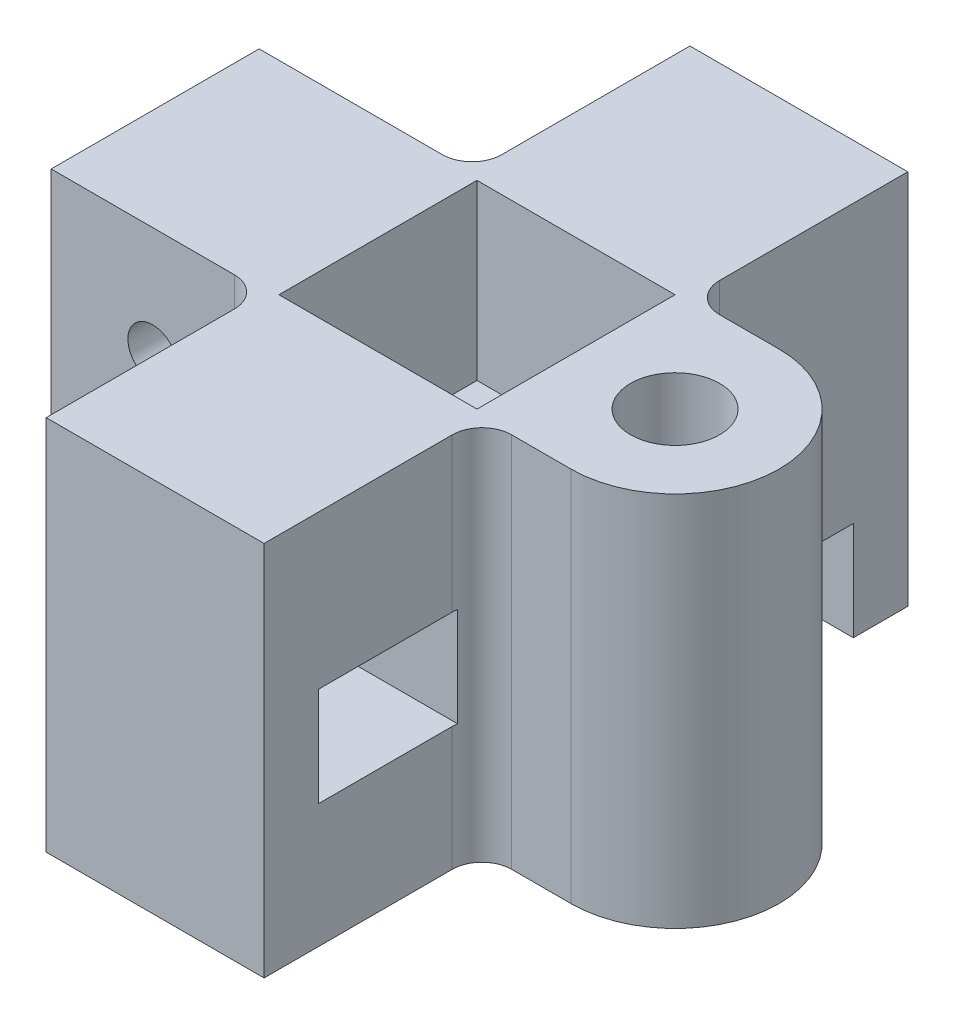
SolidWorks part; units mm, degrees
ref_plane "Front" through (0, 0, 0) normal (0, 0, 1) x (1, 0, 0)
ref_plane "Top" through (0, 0, 0) normal (0, 1, 0) x (1, 0, 0)
ref_plane "Right" through (0, 0, 0) normal (1, 0, 0) x (0, 0, -1)
sketch "Sketch1" plane through (0, 0, 0) normal (0, 1, 0) x (1, 0, 0)
  line L1 (-32.5, 32.5) -> (32.5, 32.5)
  line L2 (-32.5, 32.5) -> (-32.5, -32.5)
  line L3 (-32.5, -32.5) -> (32.5, -32.5)
  line L4 (32.5, 32.5) -> (32.5, -32.5)
  line L5 (-32.5, 32.5) -> (32.5, -32.5) construction
  line L6 (-32.5, -32.5) -> (32.5, 32.5) construction
  circle A0 centre (0, 0) radius 2.5
  circle A1 centre (20, 0) radius 2.5
  point P0 (0, 0)
  dimension "D3" = 5
  dimension "D1" = 65
  dimension "D2" = 65
  dimension "D4" = 20
extrude "Boss-Extrude1" add sketch "Sketch1" along normal blind 38
sketch "Sketch3" plane through (0, 38, 0) normal (0, 1, 0) x (1, 0, 0)
  line L0 (-32.5, 10.5) -> (-11, 10.5)
  line L1 (-32.5, 32.5) -> (-32.5, -32.5) construction
  line L2 (-11, 10.5) -> (-11, 32.5)
  line L3 (32.5, 32.5) -> (-32.5, 32.5) construction
  line L4 (-11, 32.5) -> (-32.5, 32.5)
  line L5 (-32.5, 32.5) -> (-32.5, 10.5)
  line L6 (0, -50) -> (0, 50) construction
  line L8 (11, 32.5) -> (32.5, 32.5)
  line L9 (11, 10.5) -> (11, 32.5)
  line L11 (-50, 0) -> (50, 0) construction
  line L13 (11, -10.5) -> (11, -32.5)
  line L14 (11, -32.5) -> (32.5, -32.5)
  line L15 (32.5, -32.5) -> (32.5, 32.5)
  line L16 (-32.5, -32.5) -> (-32.5, -10.5)
  line L17 (-11, -32.5) -> (-32.5, -32.5)
  line L18 (-11, -10.5) -> (-11, -32.5)
  line L19 (-32.5, -10.5) -> (-11, -10.5)
  line L20 (11, 10.5) -> (20, 10.5)
  line L21 (20, -10.5) -> (11, -10.5)
  arc A0 (20, 10.5) -> (20, -10.5) centre (20, 0) cw
  circle A1 centre (20, 0) radius 2.5 construction
  dimension "D1" = 11
  dimension "D2" = 22
extrude "Cut-Extrude2" cut sketch "Sketch3" against normal through all
sketch "Sketch4" plane through (0, 0, 0) normal (0, 0, 1) x (1, 0, 0)
  line L0 (-11, 0) -> (11, 0) construction
  line L5 (-11, 38) -> (-32.5, 38) construction
  circle A0 centre (-22.25, 27) radius 2.5
  point P4 (0, 0)
  dimension "D1" = 5
  dimension "D2" = 22.25
  dimension "D3" = 11
extrude "Cut-Extrude3" cut sketch "Sketch4" against normal through all both and the other way through all
sketch "Sketch6" plane through (0, 0, 0) normal (1, 0, 0) x (0, 0, -1)
  line L0 (-27, 22.5) -> (-13, 22.5)
  line L1 (-13, 22.5) -> (-13, 12.5)
  line L2 (-13, 12.5) -> (-27, 12.5)
  line L3 (-27, 12.5) -> (-27, 22.5)
  line L4 (13, 10) -> (27, 10)
  line L5 (27, 10) -> (27, 0)
  line L6 (27, 0) -> (13, 0)
  line L7 (13, 0) -> (13, 10)
  line L19 (32.5, 0) -> (10.5, 0) construction
  line L20 (10.5, 0) -> (10.5, 38) construction
  line L21 (-10.5, 0) -> (-10.5, 38) construction
  line L22 (27, 10) -> (13, 0) construction
  line L23 (13, 10) -> (27, 0) construction
  line L24 (-13, 22.5) -> (-27, 12.5) construction
  line L25 (-27, 22.5) -> (-13, 12.5) construction
  point P8 (20, 10)
  point P11 (-20, 22.5)
  point P16 (-20, 17.5)
  point P17 (20, 5)
  dimension "D1" = 14
  dimension "D2" = 10
  dimension "D3" = 12.5
  dimension "D4" = 9.5
  dimension "D5" = 9.5
extrude "Cut-Extrude4" cut sketch "Sketch6" against normal through all both and the other way through all
sketch "Sketch7" plane through (0, 38, 0) normal (0, 1, 0) x (1, 0, 0)
  line L1 (-10, 10) -> (10, 10)
  line L2 (-10, 10) -> (-10, -10)
  line L3 (-10, -10) -> (10, -10)
  line L4 (10, 10) -> (10, -10)
  line L5 (-10, 10) -> (10, -10) construction
  line L6 (-10, -10) -> (10, 10) construction
  point P0 (0, 0)
  dimension "D1" = 20
extrude "Cut-Extrude5" cut sketch "Sketch7" against normal blind 17.5
fillet "Fillet1" radius 3 4 edges at (11, 19, -10.5) (11, 19, 10.5) (-11, 19, 10.5) (-11, 19, -10.5)
sketch "Sketch8" plane through (0, 38, 0) normal (0, 1, 0) x (1, 0, 0)
  circle A0 centre (20, 0) radius 4.5
  circle A1 centre (0, 0) radius 4.5
  dimension "D1" = 9
extrude "Cut-Extrude6" cut sketch "Sketch8" against normal offset from surface (23 mm away) 15 up to face at (20, 0, 2.5)
